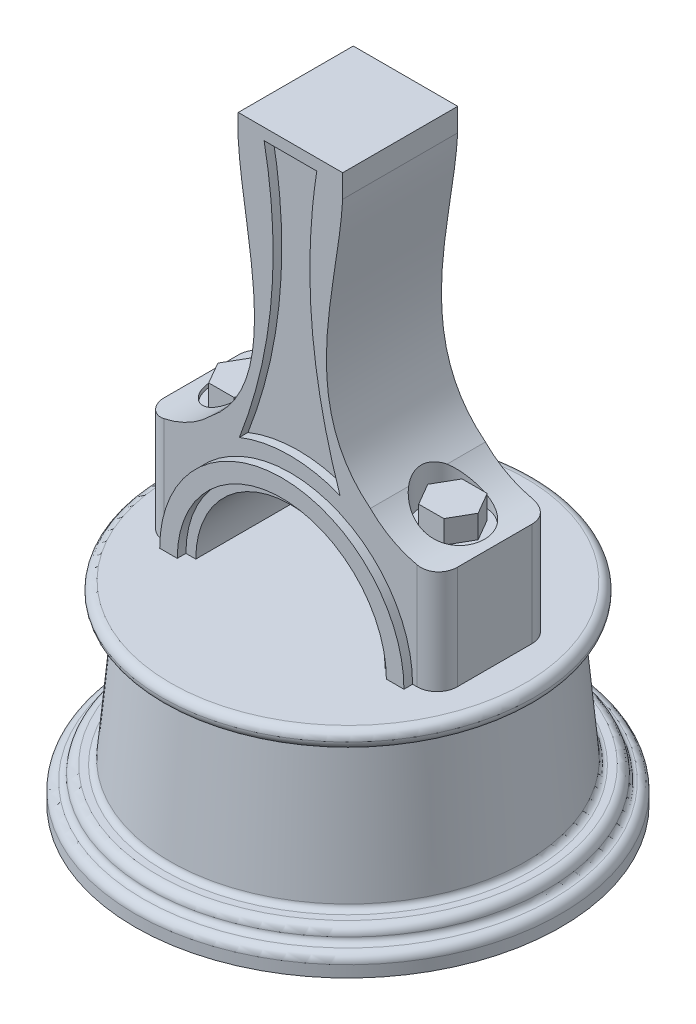
SolidWorks part; units mm, degrees
ref_plane "Front Plane" through (0, 0, 0) normal (0, 0, 1) x (1, 0, 0)
ref_plane "Top Plane" through (0, 0, 0) normal (0, 1, 0) x (1, 0, 0)
ref_plane "Right Plane" through (0, 0, 0) normal (1, 0, 0) x (0, 0, -1)
sketch "Sketch3" plane through (0, 0, 0) normal (0, 0, 1) x (1, 0, 0)
  line L0 (0, 202.5656) -> (0, 0)
  line L7 (0, 0) -> (164.321, 0)
  line L8 (164.321, 0) -> (145.978, 202.5656)
  line L9 (145.978, 202.5656) -> (0, 202.5656)
revolve "Revolve1" add sketch "Sketch3" angle 360 about L0
sketch "Sketch4" plane through (0, 202.5656, 0) normal (0, 1, 0) x (1, 0, 0)
  circle A0 centre (0, 0) radius 164.321
extrude "Boss-Extrude1" add sketch "Sketch4" along normal blind 14.986
fillet "Fillet2" radius 7.62 2 edges at (0, 202.5656, 145.978) (0, 202.5656, 164.321)
fillet "Fillet3" radius 7.62 1 edges at (0, 217.5516, 164.321)
sketch "Sketch5" plane through (0, 0, 0) normal (0, 0, 1) x (1, 0, 0)
  line L1 (-265.1498, 19.7558) -> (252.9239, 19.7558)
  line L2 (-265.1498, 19.7558) -> (-265.1498, -42.138)
  line L3 (-265.1498, -42.138) -> (252.9239, -42.138)
  line L4 (252.9239, 19.7558) -> (252.9239, -42.138)
extrude "Cut-Extrude1" cut sketch "Sketch5" along normal blind 293.37 and the other way blind 364.998
sketch "Sketch9" plane through (0, 0, 0) normal (0, 0, 1) x (1, 0, 0)
  line L1 (-203.8826, 64.1269) -> (212.6882, 64.1269)
  line L2 (-203.8826, 64.1269) -> (-203.8826, -51.0227)
  line L3 (-203.8826, -51.0227) -> (212.6882, -51.0227)
  line L4 (212.6882, 64.1269) -> (212.6882, -51.0227)
extrude "Cut-Extrude3" cut sketch "Sketch9" against normal blind 323.342 and the other way blind 203.2
sketch "Sketch10" plane through (0, 0, 0) normal (0, 0, 1) x (1, 0, 0)
  line L1 (-175.1109, 76.4993) -> (182.1861, 76.4993)
  line L2 (-175.1109, 76.4993) -> (-175.1109, 20.34)
  line L3 (-175.1109, 20.34) -> (182.1861, 20.34)
  line L4 (182.1861, 76.4993) -> (182.1861, 20.34)
extrude "Cut-Extrude4" cut sketch "Sketch10" against normal blind 314.452 and the other way blind 265.684
sketch "Sketch11" plane through (0, 76.4993, 0) normal (0, -1, 0) x (1, 0, 0)
  circle A0 centre (0, 0) radius 175.7977
extrude "Boss-Extrude5" add sketch "Sketch11" along normal blind 12.192
fillet "Fillet4" radius 7.62 1 edges at (0, 76.4993, -175.7977)
fillet "Fillet5" radius 5.08 1 edges at (0, 76.4993, -157.3937)
sketch "Sketch12" plane through (0, 64.3073, 0) normal (0, -1, 0) x (1, 0, 0)
  circle A0 centre (0, 0) radius 188.0809
extrude "Boss-Extrude6" add sketch "Sketch12" along normal blind 17.78
fillet "Fillet6" radius 7.62 1 edges at (0, 64.3073, -188.0809)
fillet "Fillet7" radius 5.08 1 edges at (0, 64.3073, -175.7977)
sketch "Sketch13" plane through (0, 0, 0) normal (0, 0, 1) x (1, 0, 0)
  line L0 (-129.5273, 217.5516) -> (-129.5273, 308.9916)
  line L1 (156.7053, 217.5516) -> (-156.7053, 217.5516) construction
  line L2 (129.5273, 217.5516) -> (129.5273, 308.9916)
  line L3 (46.119, 392.3999) -> (46.119, 577.9171)
  line L4 (-46.119, 392.3999) -> (-46.119, 577.9171)
  line L5 (46.119, 577.9171) -> (-46.119, 577.9171)
  line L6 (-129.5273, 217.5516) -> (129.5273, 217.5516)
  arc A0 (-129.5273, 308.9916) -> (-46.119, 392.3999) centre (-129.5273, 392.3999) ccw
  arc A1 (46.119, 392.3999) -> (129.5273, 308.9916) centre (129.5273, 392.3999) ccw
  arc A2 (-156.7053, 217.5516) -> (-164.321, 210.1856) centre (-156.7053, 209.9316) ccw construction
  arc A3 (164.321, 210.1856) -> (156.7053, 217.5516) centre (156.7053, 209.9316) ccw construction
  dimension "D1" = 91.44
  dimension "D2" = 27.178
  dimension "D3" = 27.178
extrude "Boss-Extrude7" add sketch "Sketch13" against normal blind 50.8 and the other way blind 50.8
sketch "Sketch14" plane through (0, 0, 50.8) normal (0, 0, 1) x (1, 0, 0)
  line L0 (156.7053, 217.5516) -> (-156.7053, 217.5516) construction
  line L1 (-83.6057, 217.5516) -> (83.6057, 217.5516)
  arc A0 (83.6057, 217.5516) -> (-83.6057, 217.5516) centre (0, 217.5516) ccw
extrude "Cut-Extrude5" cut sketch "Sketch14" against normal blind 152.4
sketch "Sketch15" plane through (0, 0, 50.8) normal (0, 0, 1) x (1, 0, 0)
  line L0 (-46.119, 577.9171) -> (-98.3621, 577.9171)
  line L1 (-98.3621, 577.9171) -> (-70.5487, 333.4213)
  arc A0 (-129.5273, 308.9916) -> (-46.119, 392.3999) centre (-129.5273, 392.3999) ccw construction
  spline S0 degree 3 poles (-46.119, 577.9171) (-50.9018, 507.403) (2.4967, 391.4378) (-70.5487, 333.4213) knots 0 0 0 0 1 1 1 1
extrude "Cut-Extrude7" cut sketch "Sketch15" against normal blind 152.4
mirror "Mirror3" about plane through (0, 0, 0) normal (1, 0, 0) of "Cut-Extrude7"
sketch "Sketch16" plane through (0, 0, 50.8) normal (0, 0, 1) x (1, 0, 0)
  line L2 (156.7053, 217.5516) -> (-156.7053, 217.5516) construction
  line L3 (-92.3309, 217.5516) -> (-107.8362, 217.5516)
  line L4 (107.8362, 217.5516) -> (92.3309, 217.5516)
  arc A2 (92.3309, 217.5516) -> (-92.3309, 217.5516) centre (0, 217.5516) ccw
  arc A3 (107.8362, 217.5516) -> (-107.8362, 217.5516) centre (0, 217.5516) ccw
extrude "Boss-Extrude8" add sketch "Sketch16" along normal blind 7.62
mirror "Mirror4" about plane through (0, 0, 0) normal (0, 0, 1) of "Boss-Extrude8"
sketch "Sketch17" plane through (0, 0, 50.8) normal (0, 0, 1) x (1, 0, 0)
  line L0 (-23.259, 567.7715) -> (23.259, 567.7715)
  line L1 (-46.119, 577.9171) -> (-46.119, 557.6258) construction
  line L2 (46.119, 557.6258) -> (46.119, 577.9171) construction
  arc A0 (43.7627, 329.8615) -> (-45.1111, 329.8615) centre (-0.6742, 218.5653) ccw
  spline S0 degree 2 poles (43.7627, 329.8615) (4.3035, 447.2292) (23.259, 567.7715) knots 0 0 0 1 1 1
  spline S1 degree 2 poles (-45.1111, 329.8615) (0.095, 446.7885) (-23.259, 567.7715) knots 0 0 0 1 1 1
  point P9 (-46.119, 567.7715)
  dimension "D1" = 22.86
  dimension "D2" = 22.86
extrude "Cut-Extrude8" cut sketch "Sketch17" against normal blind 7.62
mirror "Mirror5" about plane through (0, 0, 0) normal (0, 0, 1) of "Cut-Extrude8"
sketch "Sketch19" plane through (0, 577.9171, 0) normal (0, 1, 0) x (1, 0, 0)
  line L0 (-129.5273, -50.8) -> (-129.5273, 50.8) construction
  line L1 (129.5273, -50.8) -> (129.5273, 50.8) construction
  circle A0 centre (-92.6973, 0) radius 27.94
  circle A1 centre (92.6973, 0) radius 27.94
  dimension "D1" = 36.83
  dimension "D2" = 36.83
  dimension "D3" = 55.88
extrude "Cut-Extrude9" cut sketch "Sketch19" against normal blind 271.78
sketch "Sketch20" plane through (0, 306.1371, 0) normal (0, 1, 0) x (1, 0, 0)
  line L1 (-114.8742, 0) -> (-103.7857, -19.2058)
  line L2 (-103.7857, -19.2058) -> (-81.6088, -19.2058)
  line L3 (-81.6088, -19.2058) -> (-70.5203, 0)
  line L4 (-70.5203, 0) -> (-81.6088, 19.2058)
  line L5 (-81.6088, 19.2058) -> (-103.7857, 19.2058)
  line L6 (-103.7857, 19.2058) -> (-114.8742, 0)
  line L7 (70.5204, -0.0765) -> (81.6751, -19.2439)
  line L8 (81.6751, -19.2439) -> (103.8519, -19.1675)
  line L9 (103.8519, -19.1675) -> (114.8741, 0.0765)
  line L10 (114.8741, 0.0765) -> (103.7194, 19.2439)
  line L11 (103.7194, 19.2439) -> (81.5426, 19.1675)
  line L12 (81.5426, 19.1675) -> (70.5204, -0.0765)
  circle A0 centre (-92.6973, 0) radius 19.2058 construction
  circle A1 centre (92.6973, 0) radius 19.2058 construction
extrude "Boss-Extrude9" add sketch "Sketch20" along normal blind 20.32
fillet "Fillet8" radius 17.78 4 edges at (129.5273, 263.2716, 50.8) (-129.5273, 263.2716, -50.8) (-129.5273, 263.2716, 50.8) (129.5273, 263.2716, -50.8)
